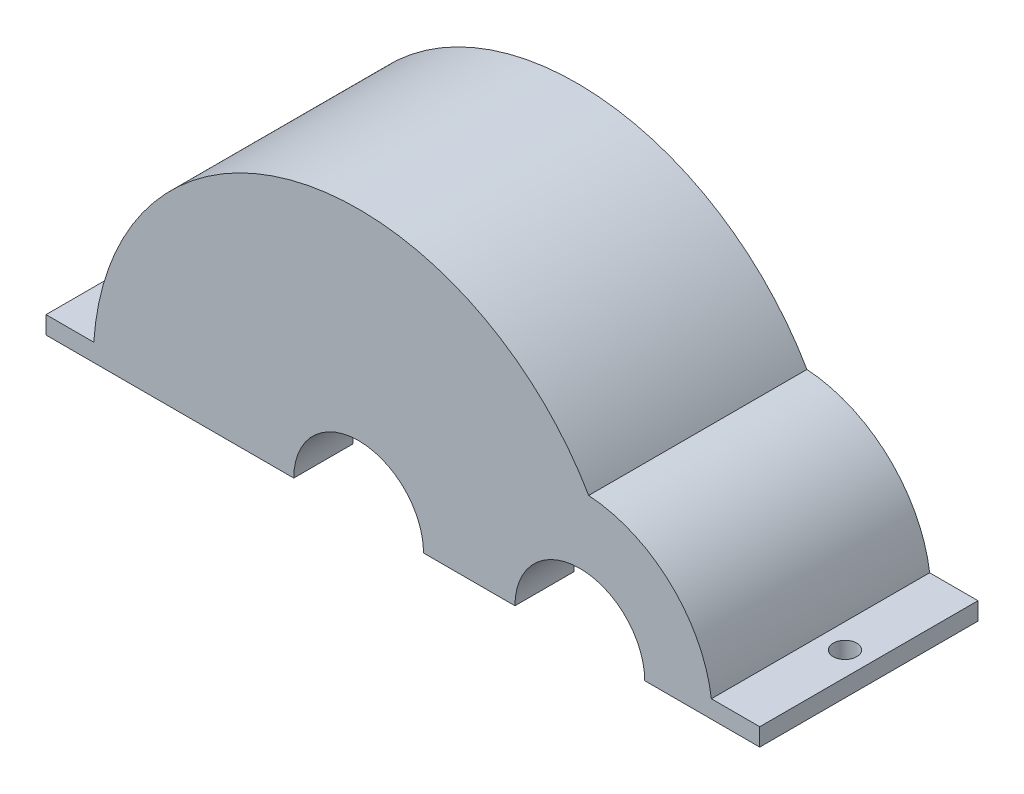
SolidWorks part; units mm, degrees
ref_plane "Front Plane" through (0, 0, 0) normal (0, 0, 1) x (1, 0, 0)
ref_plane "Top Plane" through (0, 0, 0) normal (0, 1, 0) x (1, 0, 0)
ref_plane "Right Plane" through (0, 0, 0) normal (1, 0, 0) x (0, 0, -1)
sketch "Sketch1" plane through (0, 0, 0) normal (0, 0, 1) x (1, 0, 0)
  line L0 (-18.75, 0) -> (18.75, 0)
  line L1 (-73.75, -5) -> (-73.75, -55)
  line L3 (-73.75, -5) -> (-73.75, 5)
  line L4 (-73.75, 5) -> (-63.4714, 5)
  line L10 (40.6874, 5) -> (51.25, 5)
  line L11 (51.25, -5) -> (51.25, 5)
  line L14 (51.25, -5) -> (51.25, -55)
  line L15 (51.25, -55) -> (-73.75, -55)
  circle A0 centre (18.75, 0) radius 7.5
  circle A1 centre (-18.75, 0) radius 30
  arc A2 (20.25, 22.4499) -> (20.25, -22.4499) centre (-18.75, 0) ccw
  arc A3 (20.25, -22.4499) -> (20.25, 22.4499) centre (18.75, 0) ccw
  circle A5 centre (18.75, 0) radius 22.5 construction
  circle A6 centre (-18.75, 0) radius 45 construction
  point P4 (0, 0)
  point P7 (-63.75, 0)
  point P10 (31.25, 0)
  point P13 (16.25, 0)
  point P19 (41.25, 0)
  dimension "D1" = 37.5
  dimension "D2" = 60
  dimension "D3" = 15
  dimension "D4" = 15
  dimension "D5" = 15
extrude "Boss-Extrude2" add sketch "Sketch1" along normal blind 27 contours A3 A2 A1 A0 | A1 | A0 region at (-27.6498, 42.6994, 0) region at (18.75, -7.2879, 0) region at (-47.9015, 0, 0)
shell "Shell5" thickness 10 removed face at (-11.25, 0, 0)
sketch "Sketch2" plane through (0, 0, 17) normal (0, 0, -1) x (-1, 0, 0)
  line L0 (-18.75, 0) -> (18.75, 0) construction
  circle A0 centre (-18.75, 0) radius 4
  circle A1 centre (18.75, 0) radius 4
  point P4 (0, 0)
sketch "Sketch4" plane through (0, 0, 0) normal (0, 0, -1) x (-1, 0, 0)
  arc A0 (-20.25, 22.4499) -> (-20.25, -22.4499) centre (-18.75, 0) ccw construction
  arc A1 (-20.25, -22.4499) -> (-20.25, 22.4499) centre (18.75, 0) ccw construction
  arc A4 (-20.25, 22.4499) -> (-20.25, -22.4499) centre (-18.75, 0) ccw
  arc A5 (-20.25, -22.4499) -> (-20.25, 22.4499) centre (18.75, 0) ccw
extrude "Boss-Extrude3" add sketch "Sketch4" along normal blind 10
sketch "Sketch5" plane through (0, 0, -10) normal (0, 0, -1) x (-1, 0, 0)
  line L0 (-18.75, 0) -> (18.75, 0) construction
  line L1 (-18.75, 0) -> (18.75, 0)
  circle A6 centre (-18.75, 0) radius 11
  circle A7 centre (18.75, 0) radius 11
extrude "Cut-Extrude2" cut sketch "Sketch5" against normal through all contours A6 | A7 region at (-18.75, 10.6889, -10) region at (29.4389, 0, -10)
sketch "Sketch8" plane through (0, 0, -10) normal (0, 0, -1) x (-1, 0, 0)
  line L0 (-41.25, 0) -> (63.75, 0) construction
  line L1 (11.25, 0) -> (11.25, 61.6014) construction
  line L2 (-41.25, 0) -> (-41.25, -50)
  line L3 (-41.25, -50) -> (63.75, -50)
  line L4 (63.75, -50) -> (63.75, 0)
  arc A0 (-20.25, 22.4499) -> (-20.25, -22.4499) centre (-18.75, 0) ccw construction
  arc A1 (-20.25, -22.4499) -> (-20.25, 22.4499) centre (18.75, 0) ccw construction
  arc A2 (-20.25, -22.4499) -> (63.75, 0) centre (18.75, 0) ccw
  arc A3 (-41.25, 0) -> (-20.25, -22.4499) centre (-18.75, 0) ccw
extrude "Boss-Extrude4" add sketch "Sketch8" against normal up to surface (37 mm away) up to face at (7.75, 0, 27)
sketch "Sketch9" plane through (0, 0, 0) normal (0, 1, 0) x (1, 0, 0)
  line L0 (-63.75, -8.5) -> (41.25, -8.5) construction
  line L5 (41.25, -27) -> (41.25, 10) construction
  line L6 (-11.25, -8.5) -> (-11.25, 40.864) construction
  line L11 (-63.75, -8.5) -> (-58.75, -8.5) construction
  line L12 (-58.75, -8.5) -> (-58.75, 10)
  line L13 (20.25, 10) -> (-63.75, 10) construction
  line L14 (-58.75, 10) -> (-71.75, 10)
  line L15 (-71.75, 10) -> (-71.75, -27)
  line L16 (-71.75, -27) -> (-58.75, -27)
  line L17 (-63.75, -27) -> (20.25, -27) construction
  line L18 (-58.75, -27) -> (-58.75, -8.5)
  line L19 (36.25, -27) -> (36.25, -8.5)
  line L20 (49.25, -27) -> (36.25, -27)
  line L21 (49.25, 10) -> (49.25, -27)
  line L22 (36.25, 10) -> (49.25, 10)
  line L23 (36.25, -8.5) -> (36.25, 10)
extrude "Boss-Extrude5" add sketch "Sketch9" along normal blind 3 and the other way up to surface (50 mm away) contours L16 L18 L12 L14 L15 | L23 L19 L20 L21 L22 region at (-65.25, 0, 8.5) region at (42.75, 0, 8.5) other way up to face at (-11.25, -50, 8.5)
sketch "Sketch10" plane through (0, 3, 0) normal (0, 1, 0) x (1, 0, 0)
  line L0 (-71.75, -8.5) -> (49.25, -8.5) construction
  line L1 (-71.75, 10) -> (-71.75, -27) construction
  line L2 (49.25, 10) -> (49.25, -27) construction
  line L3 (-11.25, -8.5) -> (-11.25, 28.9746) construction
  line L4 (-71.75, -8.5) -> (-63.6499, -8.5)
  line L5 (-63.6499, 10) -> (-63.6499, -27) construction
  circle A0 centre (-67.6999, -8.5) radius 2
  circle A1 centre (45.1999, -8.5) radius 2
extrude "Cut-Extrude3" cut sketch "Sketch10" against normal blind 10 contours A1 | A0
ref_plane "Plane1" through (0, 0, 0) normal (0, 1, 0) x (1, 0, 0)
sketch "Sketch11" plane through (0, 0, 0) normal (0, 1, 0) x (1, 0, 0)
  line L1 (-71.75, 10) -> (49.25, 10)
  line L2 (-71.75, 10) -> (-71.75, -27)
  line L3 (-71.75, -27) -> (49.25, -27)
  line L4 (49.25, 10) -> (49.25, -27)
extrude "Cut-Extrude4" cut sketch "Sketch11" against normal through all
